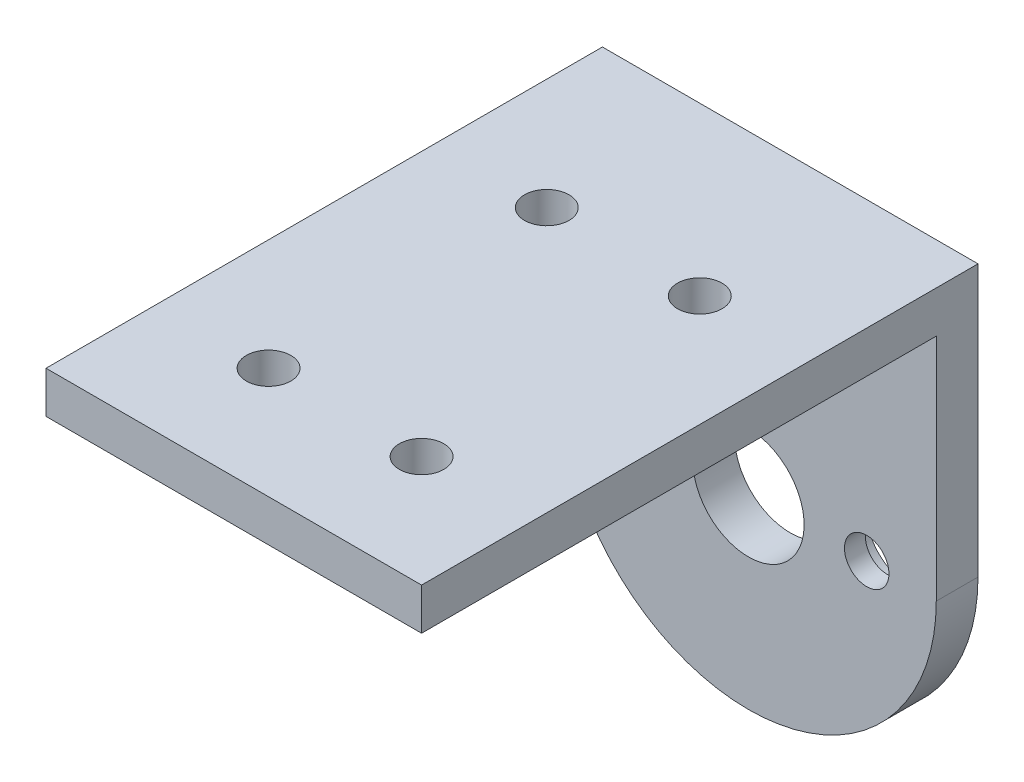
SolidWorks part; units mm, degrees
ref_plane "前视基准面" through (0, 0, 0) normal (0, 0, 1) x (1, 0, 0)
ref_plane "上视基准面" through (0, 0, 0) normal (0, 1, 0) x (1, 0, 0)
ref_plane "右视基准面" through (0, 0, 0) normal (1, 0, 0) x (0, 0, -1)
sketch "Model" plane through (0, 0, 0) normal (0, 0, 1) x (1, 0, 0)
  line L0 (2619.7667, 1592.8264) -> (2619.7667, 1612.3264)
  line L1 (2592.7667, 1592.8264) -> (2592.7667, 1612.3264)
  line L2 (2592.7667, 1612.3264) -> (2619.7667, 1612.3264)
  circle A0 centre (2606.2667, 1592.8264) radius 3.5
  arc A1 (2592.7667, 1592.8264) -> (2619.7667, 1592.8264) centre (2606.2667, 1592.8264) ccw
  dimension "D1" = 19.5
extrude "凸台-拉伸1" add sketch "Model" along normal blind 40
sketch "草图3" plane through (2619.7667, 0, 0) normal (1, 0, 0) x (0, 0, -1)
  line L0 (-40, 1592.8264) -> (-40, 1612.3264) construction
  line L1 (-40, 1609.3264) -> (-3, 1609.3264)
  line L2 (-40, 1609.3264) -> (-40, 1572.3264)
  line L3 (-40, 1572.3264) -> (-3, 1572.3264)
  line L4 (-3, 1609.3264) -> (-3, 1572.3264)
  line L5 (-40, 1612.3264) -> (0, 1612.3264) construction
  line L6 (0, 1592.8264) -> (0, 1612.3264) construction
  dimension "D1" = 3
  dimension "D2" = 3
  dimension "D3" = 40
extrude "切除-拉伸1" cut sketch "草图3" against normal blind 40
sketch "草图4" plane through (0, 1612.3264, 0) normal (0, 1, 0) x (1, 0, 0)
  line L6 (2619.7667, -40) -> (2619.7667, -32)
  circle A0 centre (2600.7667, -32) radius 1.5
  circle A1 centre (2611.7667, -32) radius 1.5
  circle A2 centre (2600.7667, -12) radius 1.5
  circle A3 centre (2611.7667, -12) radius 1.5
  dimension "D7" = 3
  dimension "D8" = 3
  dimension "D9" = 3
  dimension "D10" = 3
extrude "切除-拉伸2" cut sketch "草图4" against normal blind 40 contours A0 | A1 | A3 | A2
sketch "Sketch1" plane through (0, 0, 0) normal (0, 0, -1) x (-1, 0, 0)
  circle A0 centre (-2606.2667, 1592.8264) radius 4
extrude "Cut-Extrude1" cut sketch "Sketch1" against normal blind 10
sketch "Sketch2" plane through (0, 0, 0) normal (0, 0, -1) x (-1, 0, 0)
  circle A0 centre (-2614.7667, 1592.8264) radius 1.6
  circle A1 centre (-2597.7667, 1592.8264) radius 1.6
extrude "Cut-Extrude2" cut sketch "Sketch2" against normal blind 10
sketch "Sketch3" plane through (0, 0, 0) normal (0, 0, -1) x (-1, 0, 0)
  circle A0 centre (-2597.7667, 1592.8264) radius 3
  circle A1 centre (-2614.7667, 1592.8264) radius 3
extrude "Cut-Extrude3" cut sketch "Sketch3" against normal blind 1.5
sketch "Sketch4" plane through (0, 1612.3264, 0) normal (0, 1, 0) x (1, 0, 0)
  circle A0 centre (2600.7667, -12) radius 1.6
  circle A1 centre (2611.7667, -12) radius 1.6
  circle A2 centre (2600.7667, -32) radius 1.6
  circle A3 centre (2611.7667, -32) radius 1.6
extrude "Cut-Extrude4" cut sketch "Sketch4" against normal blind 10
